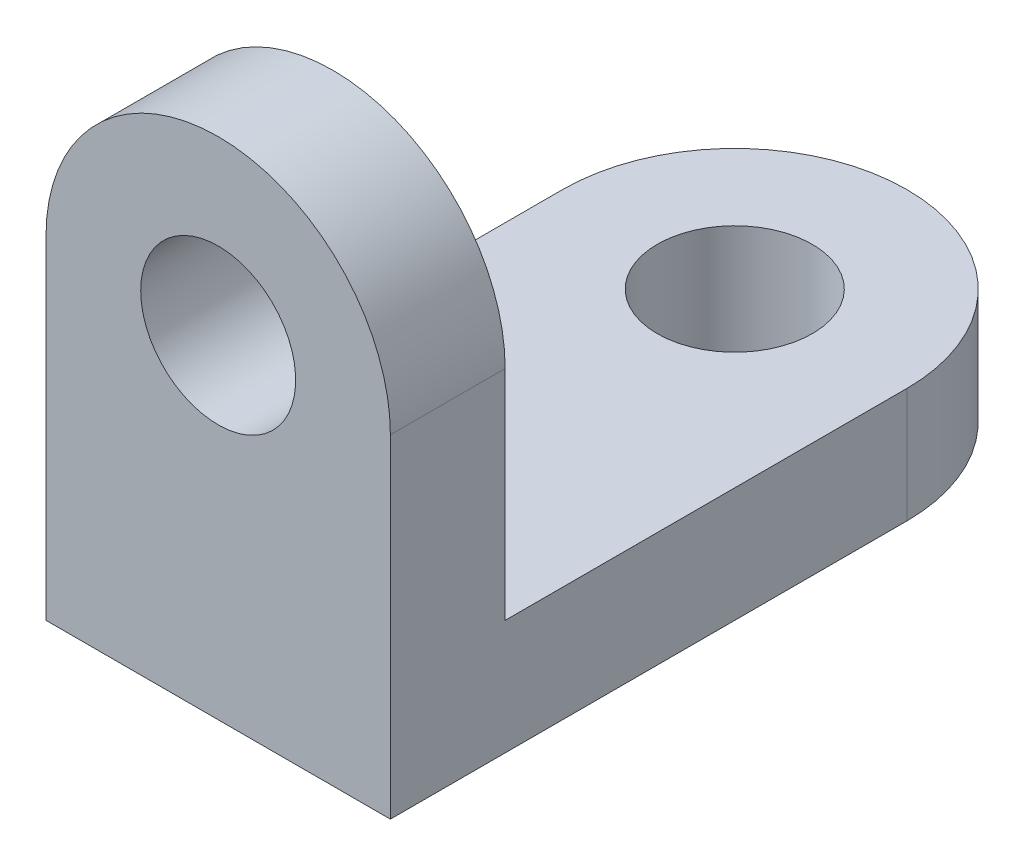
SolidWorks part; units mm, degrees
ref_plane "Plan de face" through (0, 0, 0) normal (0, 0, 1) x (1, 0, 0)
ref_plane "Plan de dessus" through (0, 0, 0) normal (0, 1, 0) x (1, 0, 0)
ref_plane "Plan de droite" through (0, 0, 0) normal (1, 0, 0) x (0, 0, -1)
sketch "Esquisse1" plane through (0, 0, 0) normal (0, 1, 0) x (1, 0, 0)
  line L1 (-7.5, 16.7397) -> (7.5, 16.7397)
  line L2 (-7.5, 16.7397) -> (-7.5, -13.2603)
  line L3 (-7.5, -13.2603) -> (7.5, -13.2603)
  line L4 (7.5, 16.7397) -> (7.5, -13.2603)
  line L5 (-7.5, 16.7397) -> (7.5, -13.2603) construction
  line L6 (-7.5, -13.2603) -> (7.5, 16.7397) construction
  point P0 (0, 1.7397)
  dimension "D1" = 15
  dimension "D2" = 30
extrude "Boss.-Extru.1" add sketch "Esquisse1" along normal blind 5
sketch "Esquisse2" plane through (0, 5, 0) normal (0, 1, 0) x (1, 0, 0)
  line L0 (7.5, -13.2603) -> (7.5, 16.7397) construction
  line L1 (-7.5, 16.7397) -> (-7.5, -13.2603) construction
  line L2 (-7.5, -13.2603) -> (7.5, -13.2603) construction
  line L3 (7.5, -13.2603) -> (7.5, -8.2603)
  line L4 (-7.5, -8.2603) -> (-7.5, -13.2603)
  line L5 (-7.5, -13.2603) -> (7.5, -13.2603)
  line L6 (-7.5, -8.2603) -> (7.5, -8.2603)
  dimension "D1" = 5
extrude "Boss.-Extru.2" add sketch "Esquisse2" along normal blind 17
fillet "Congé1" 2 edges at (-7.5, 2.5, -16.7397) (7.5, 2.5, -16.7397) type full round first side face at (-7.5, 9, 1.5936) second side face at (7.5, 9, 1.5936) middle face at (0, 2.5, -16.7397)
fillet "Congé3" 2 edges at (-7.5, 22, 10.7603) (7.5, 22, 10.7603) type full round first side face at (-7.5, 9, 4.0936) second side face at (7.5, 9, 4.0936) middle face at (0, 22, 10.7603)
sketch "Esquisse3" plane through (0, 5, 0) normal (0, 1, 0) x (1, 0, 0)
  circle A0 centre (0, 9.2397) radius 3.375
  dimension "D1" = 6.75
extrude "Enlèv. mat.-Extru.1" cut sketch "Esquisse3" against normal blind 10
sketch "Esquisse4" plane through (0, 0, 8.2603) normal (0, 0, -1) x (-1, 0, 0)
  circle A0 centre (0, 14.5) radius 3.375
  dimension "D1" = 6.75
extrude "Enlèv. mat.-Extru.2" cut sketch "Esquisse4" against normal blind 10
